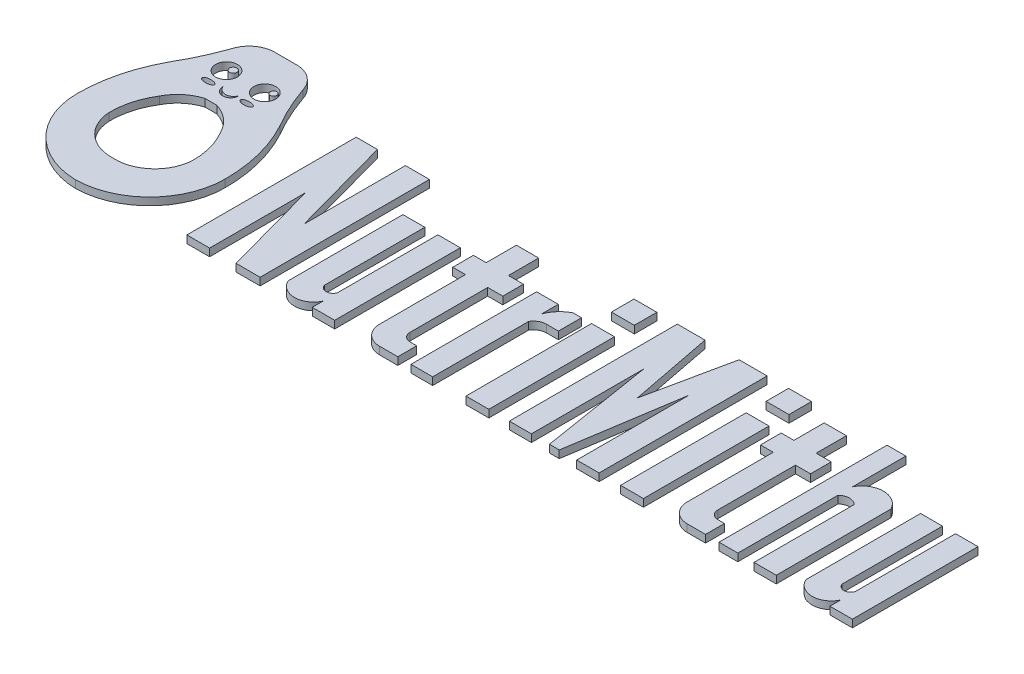
SolidWorks part; units mm, degrees
ref_plane "Front Plane" through (0, 0, 0) normal (0, 0, 1) x (1, 0, 0)
ref_plane "Top Plane" through (0, 0, 0) normal (0, 1, 0) x (1, 0, 0)
ref_plane "Right Plane" through (0, 0, 0) normal (1, 0, 0) x (0, 0, -1)
sketch "Sketch2" plane through (0, 0, 0) normal (0, 1, 0) x (1, 0, 0)
  line L0 (1.6932, 0) -> (6.6932, 0) construction
  dimension "D1" = 5
sketch "Sketch4" plane through (0, 0, 0) normal (0, 1, 0) x (1, 0, 0)
  line L0 (9.6226, 17.964) -> (9.6226, 26.3934) construction
  line L1 (9.1082, 26.2928) -> (10.137, 26.2928)
  line L2 (9.3877, 23.3253) -> (9.8574, 23.3253)
  line L3 (13.7169, 18.2788) -> (13.7169, 24.9914)
  line L4 (13.7169, 24.9914) -> (14.5592, 24.9914)
  line L5 (14.5592, 24.9914) -> (15.6676, 20.9688)
  line L6 (15.6676, 20.9688) -> (15.6676, 24.9914)
  line L7 (15.6676, 24.9914) -> (16.6208, 24.9914)
  line L8 (16.6208, 24.9914) -> (16.6208, 18.2788)
  line L9 (16.6208, 18.2788) -> (15.6676, 18.2788)
  line L10 (15.6676, 18.2788) -> (14.6187, 22.0855)
  line L11 (14.6187, 22.0855) -> (14.6187, 18.2788)
  line L12 (14.6187, 18.2788) -> (13.7169, 18.2788)
  line L13 (17.3009, 23.2589) -> (17.3009, 18.7102)
  line L14 (17.3009, 23.2589) -> (18.1698, 23.2589)
  line L15 (18.1698, 23.2589) -> (18.1698, 19.2794)
  line L17 (18.6877, 19.2794) -> (18.6877, 23.2589)
  line L18 (18.6877, 23.2589) -> (19.5776, 23.2589)
  line L19 (19.5776, 23.2589) -> (19.5776, 18.2788)
  line L20 (19.5776, 18.2788) -> (18.6877, 18.2788)
  line L21 (18.6877, 18.2788) -> (18.6877, 18.7049)
  line L22 (37.8224, 23.2589) -> (37.8224, 18.7102)
  line L23 (37.8224, 23.2589) -> (38.6914, 23.2589)
  line L24 (38.6914, 23.2589) -> (38.6914, 19.2794)
  line L25 (39.2093, 19.2794) -> (39.2093, 23.2589)
  line L26 (39.2093, 23.2589) -> (40.0992, 23.2589)
  line L27 (40.0992, 23.2589) -> (40.0992, 18.2788)
  line L28 (39.2093, 18.2788) -> (39.2093, 18.7049)
  line L29 (40.0992, 18.2788) -> (39.2093, 18.2788)
  line L30 (21.4826, 19.364) -> (21.4826, 22.4393)
  line L31 (21.4826, 22.4393) -> (22.0793, 22.4393)
  line L32 (22.0793, 22.4393) -> (22.0793, 23.2589)
  line L33 (22.0793, 23.2589) -> (21.4826, 23.2589)
  line L34 (21.4826, 23.2589) -> (21.4826, 24.459)
  line L35 (21.4826, 24.459) -> (20.6013, 24.459)
  line L36 (20.6013, 24.459) -> (20.6013, 23.2589)
  line L37 (20.6013, 23.2589) -> (20.0964, 23.2589)
  line L38 (20.0964, 23.2589) -> (20.0964, 22.4393)
  line L39 (20.0964, 22.4393) -> (20.6013, 22.4393)
  line L40 (20.6013, 22.4393) -> (20.6013, 19.0288)
  line L41 (21.8178, 19.0288) -> (22.0793, 19.0288)
  line L42 (22.0793, 19.0288) -> (22.0793, 18.2788)
  line L43 (22.0793, 18.2788) -> (21.3513, 18.2788)
  line L58 (23.4607, 22.6007) -> (23.4607, 23.2589)
  line L59 (22.6004, 23.2589) -> (22.6004, 18.2788)
  line L60 (22.6004, 18.2788) -> (23.4607, 18.2788)
  line L61 (23.4607, 18.2788) -> (23.4607, 22.0855)
  line L62 (23.9111, 22.342) -> (24.3817, 22.342)
  line L63 (24.3817, 22.342) -> (24.3817, 23.2589)
  line L64 (24.3817, 23.2589) -> (24.047, 23.2589)
  line L65 (23.4607, 23.2589) -> (22.6004, 23.2589)
  line L67 (24.7801, 23.2589) -> (25.6873, 23.2589)
  line L68 (24.7801, 23.2589) -> (24.7801, 18.2788)
  line L69 (24.7801, 18.2788) -> (25.6873, 18.2788)
  line L70 (25.6873, 23.2589) -> (25.6873, 18.2788)
  line L71 (24.7801, 24.9396) -> (25.6873, 24.9396)
  line L72 (24.7801, 24.9396) -> (24.7801, 24.0461)
  line L73 (24.7801, 24.0461) -> (25.6873, 24.0461)
  line L74 (25.6873, 24.9396) -> (25.6873, 24.0461)
  line L82 (26.4992, 18.2788) -> (26.4992, 24.9396)
  line L83 (26.4992, 24.9396) -> (27.5972, 24.9396)
  line L84 (27.5972, 24.9396) -> (28.2444, 21.6092)
  line L85 (28.2444, 21.6092) -> (28.9495, 24.9396)
  line L86 (28.9495, 24.9396) -> (30.059, 24.9396)
  line L87 (30.059, 24.9396) -> (30.059, 18.2788)
  line L88 (30.059, 18.2788) -> (29.1726, 18.2788)
  line L89 (29.1726, 18.2788) -> (29.1726, 22.734)
  line L90 (29.1726, 22.734) -> (28.4791, 18.2788)
  line L91 (28.4791, 18.2788) -> (28.0887, 18.2788)
  line L92 (28.0887, 18.2788) -> (27.3741, 22.734)
  line L93 (27.3741, 22.734) -> (27.3741, 18.2788)
  line L94 (27.3741, 18.2788) -> (26.4992, 18.2788)
  line L95 (34.8125, 24.9396) -> (35.5593, 24.9396)
  line L96 (35.5593, 24.9396) -> (35.5593, 22.8248)
  line L97 (34.8125, 24.9396) -> (34.8125, 18.2788)
  line L98 (34.8125, 18.2788) -> (35.5593, 18.2788)
  line L99 (35.5593, 18.2788) -> (35.5593, 22.2462)
  line L100 (36.2004, 22.2462) -> (36.2004, 18.2788)
  line L101 (36.2004, 18.2788) -> (37.0818, 18.2788)
  line L102 (37.0818, 18.2788) -> (37.0818, 22.8248)
  line L104 (30.9096, 24.9396) -> (31.8167, 24.9396)
  line L105 (30.9096, 24.9396) -> (30.9096, 24.0461)
  line L106 (30.9096, 24.0461) -> (31.8167, 24.0461)
  line L107 (31.8167, 24.9396) -> (31.8167, 24.0461)
  line L108 (30.9096, 23.2589) -> (31.8167, 23.2589)
  line L109 (30.9096, 23.2589) -> (30.9096, 18.2788)
  line L110 (30.9096, 18.2788) -> (31.8167, 18.2788)
  line L111 (31.8167, 23.2589) -> (31.8167, 18.2788)
  line L125 (32.8013, 23.2589) -> (32.2964, 23.2589)
  line L126 (32.8013, 24.459) -> (32.8013, 23.2589)
  line L127 (33.6826, 24.459) -> (32.8013, 24.459)
  line L128 (33.6826, 23.2589) -> (33.6826, 24.459)
  line L129 (34.2793, 23.2589) -> (33.6826, 23.2589)
  line L130 (34.2793, 22.4393) -> (34.2793, 23.2589)
  line L131 (33.6826, 22.4393) -> (34.2793, 22.4393)
  line L132 (33.6826, 19.364) -> (33.6826, 22.4393)
  line L133 (34.0178, 19.0288) -> (34.2793, 19.0288)
  line L134 (34.2793, 19.0288) -> (34.2793, 18.2788)
  line L135 (34.2793, 18.2788) -> (33.5513, 18.2788)
  line L136 (32.8013, 22.4393) -> (32.8013, 19.0288)
  line L137 (32.2964, 22.4393) -> (32.8013, 22.4393)
  line L138 (32.2964, 23.2589) -> (32.2964, 22.4393)
  arc A0 (9.6226, 17.964) -> (6.6888, 20.9462) centre (9.6827, 20.9574) cw
  arc A1 (6.6888, 20.9462) -> (7.4325, 23.8752) centre (12.7398, 20.9688) cw
  arc A2 (7.4325, 23.8752) -> (8.2074, 25.5576) centre (-0.7833, 28.6793) ccw
  arc A3 (8.2074, 25.5576) -> (9.1082, 26.2928) centre (9.197, 25.2645) cw
  circle A4 centre (8.8631, 24.7032) radius 0.4326
  circle A5 centre (10.382, 24.7032) radius 0.4326
  arc A6 (11.0377, 25.5576) -> (10.137, 26.2928) centre (10.0481, 25.2645) ccw
  arc A7 (11.8127, 23.8752) -> (11.0377, 25.5576) centre (20.0284, 28.6793) cw
  arc A8 (12.5563, 20.9462) -> (11.8127, 23.8752) centre (6.5053, 20.9688) ccw
  arc A9 (9.6226, 17.964) -> (12.5563, 20.9462) centre (9.5624, 20.9574) ccw
  arc A10 (9.3408, 24.0872) -> (9.9732, 24.0872) centre (9.657, 24.2042) ccw
  circle A11 centre (8.9813, 24.8531) radius 0.1471
  circle A12 centre (10.5839, 24.8531) radius 0.1287
  arc A13 (9.6226, 19.4537) -> (7.9707, 20.9462) centre (9.5429, 21.0258) cw
  arc A14 (7.9707, 20.9462) -> (8.4043, 22.5045) centre (10.8413, 20.9869) cw
  arc A15 (8.4043, 22.5045) -> (9.3877, 23.3253) centre (9.8759, 21.741) cw
  arc A16 (9.6226, 19.4537) -> (11.2744, 20.9462) centre (9.7022, 21.0258) ccw
  arc A17 (11.2744, 20.9462) -> (10.8408, 22.5045) centre (8.4038, 20.9869) ccw
  arc A18 (10.8408, 22.5045) -> (9.8574, 23.3253) centre (9.3692, 21.741) ccw
  arc A19 (17.3009, 18.7102) -> (18.6877, 18.7049) centre (17.9955, 19.0288) ccw
  arc A21 (18.1698, 19.2794) -> (18.6877, 19.2794) centre (18.4288, 19.364) ccw
  arc A22 (38.6914, 19.2794) -> (39.2093, 19.2794) centre (38.9504, 19.364) ccw
  arc A23 (37.8224, 18.7102) -> (39.2093, 18.7049) centre (38.5171, 19.0288) ccw
  arc A24 (20.6013, 19.0288) -> (21.3513, 18.2788) centre (21.3513, 19.0288) ccw
  arc A25 (21.4826, 19.364) -> (21.8178, 19.0288) centre (21.8178, 19.364) ccw
  arc A30 (23.9111, 22.342) -> (23.4607, 22.0855) centre (23.9111, 21.8183) ccw
  arc A31 (23.4607, 22.6007) -> (24.047, 23.2589) centre (24.6092, 22.1679) cw
  arc A32 (35.5593, 22.8248) -> (37.0818, 22.8248) centre (36.3206, 22.436) cw
  arc A33 (35.5593, 22.2462) -> (36.2004, 22.2462) centre (35.8798, 21.9257) cw
  arc A36 (33.6826, 19.364) -> (34.0178, 19.0288) centre (34.0178, 19.364) ccw
  arc A37 (32.8013, 19.0288) -> (33.5513, 18.2788) centre (33.5513, 19.0288) ccw
  arc A38 (9.3408, 24.0872) -> (9.9732, 24.0872) centre (9.657, 24.0764) ccw
  ellipse E0 centre (8.8631, 23.9812) end of major axis (9.1082, 23.9812) minor radius 0.106
  ellipse E1 centre (10.382, 23.9812) end of major axis (10.137, 23.9812) minor radius 0.106
  ellipse E2 centre (9.6226, 18.2788) end of major axis (6.734, 18.2788) minor radius 0.5686 (7.7103, 18.7049) -> (11.5348, 18.7049) ccw
  point P35 (9.6226, 26.2928)
  point P63 (9.6226, 23.3253)
  dimension "D1" = 0.2943
  dimension "D2" = 0.2575
  dimension "D3" = 0.8651
  dimension "D6" = 9.5172
  dimension "D7" = 1.0322
  dimension "D8" = 0.3371
  dimension "D9" = 1.5742
  dimension "D10" = 2.8709
  dimension "D11" = 1.6579
  dimension "D12" = 2.9939
  dimension "D13" = 6.0511
  dimension "D14" = 0.7642
  dimension "D15" = 0.2724
  dimension "D16" = 6.5053
  dimension "D21" = 6.6888
  dimension "D22" = 0.75
  dimension "D29" = 0.3352
  dimension "D32" = 0.5237
  dimension "D33" = 1.2273
  dimension "D34" = 0.8548
  dimension "D35" = 0.4533
  dimension "D72" = 0.3164
  dimension "D17" = 7.9707
  dimension "D18" = 8.2074
  dimension "D19" = 8.4038
  dimension "D20" = 8.4043
  dimension "D23" = 8.9813
  dimension "D24" = 9.197
  dimension "D25" = 9.3408
  dimension "D26" = 9.3692
  dimension "D27" = 9.3877
  dimension "D28" = 9.5429
  dimension "D30" = 9.657
  dimension "D31" = 20.0284
  dimension "D36" = 2
  dimension "D37" = 6.734
  dimension "D38" = 7.4325
  dimension "D39" = 7.7103
  dimension "D40" = 8.618
  dimension "D41" = 10.5839
  dimension "D42" = 8.8631
  dimension "D43" = 9.5624
  dimension "D44" = 17.9955
  dimension "D45" = 18.1698
  dimension "D46" = 18.4288
  dimension "D47" = 20.6013
  dimension "D48" = 22.0793
  dimension "D49" = 24.7801
  dimension "D50" = 25.6873
  dimension "D51" = 24.7032
  dimension "D52" = 24.8531
  dimension "D53" = 30.9096
  dimension "D54" = 35.5593
  dimension "D55" = 35.8798
  dimension "D56" = 36.3206
  dimension "D57" = 17.7102
  dimension "D58" = 19.4537
  dimension "D59" = 20.9869
  dimension "D60" = 21.8183
  dimension "D61" = 21.9257
  dimension "D62" = 22.1679
  dimension "D63" = 22.436
  dimension "D64" = 2
  dimension "D65" = 13.7169
  dimension "D66" = 14.5592
  dimension "D67" = 14.6187
  dimension "D68" = 15.6676
  dimension "D69" = 16.6208
  dimension "D70" = 17.3009
  dimension "D71" = 32.2964
  dimension "D75" = 19.5776
  dimension "D76" = 20.0964
  dimension "D78" = 21.4826
  dimension "D80" = 22.6004
  dimension "D81" = 23.4607
  dimension "D82" = 23.9111
  dimension "D83" = 24.047
  dimension "D84" = 24.3817
  dimension "D85" = 24.6092
  dimension "D86" = 21.6092
  dimension "D88" = 26.4992
  dimension "D89" = 27.3741
  dimension "D90" = 27.5972
  dimension "D91" = 28.0887
  dimension "D92" = 28.2444
  dimension "D93" = 28.4791
  dimension "D94" = 28.9495
  dimension "D95" = 29.1726
  dimension "D96" = 30.059
  dimension "D99" = 34.8125
  dimension "D105" = 37.8224
  dimension "D106" = 22.4393
  dimension "D109" = 22.734
  dimension "D115" = 24.0461
  dimension "D118" = 24.459
  dimension "D119" = 24.9396
extrude "Boss-Extrude1" add sketch "Sketch4" along normal blind 0.3 contours L12 L3 L4 L5 L6 L7 L8 L9 L10 L11 | L21 A19 L13 L14 L15 A21 L17 L18 L19 L20 | A24 L43 L42 L41 A25 L30 L31 L32 L33 L34 L35 L36 L37 L38 L39 L40 | L60 L61 A30 L62 L63 L64 A31 L58 L65 L59 | L69 L70 L67 L68 | L73 L74 L71 L72 | L82 L83 L84 L85 L86 L87 L88 L89 L90 L91 L92 L93 L94 | L109 L110 L111 L108 | L106 L107 L104 L105 | L136 A37 L135 L134 L133 A36 L132 L131 L130 L129 L128 L127 L126 L125 L138 L137 | L98 L99 A33 L100 L101 L102 A32 L96 L95 L97 | A23 L28 L29 L27 L26 L25 A22 L24 L23 L22
extrude "Boss-Extrude2" add sketch "Sketch4<6>" along normal blind 0.3 separate body contours A0 A1 A2 A3 L1 A6 A7 A8 A9 | A13 A14 A15 L2 A18 A17 A16 | A4 | A11 | A5 | A12 | E1 | E0 | A38 A10
sketch "Sketch4<6>" plane through (0, 0, 0) normal (0, 1, 0) x (1, 0, 0) same geometry as "Sketch4"
